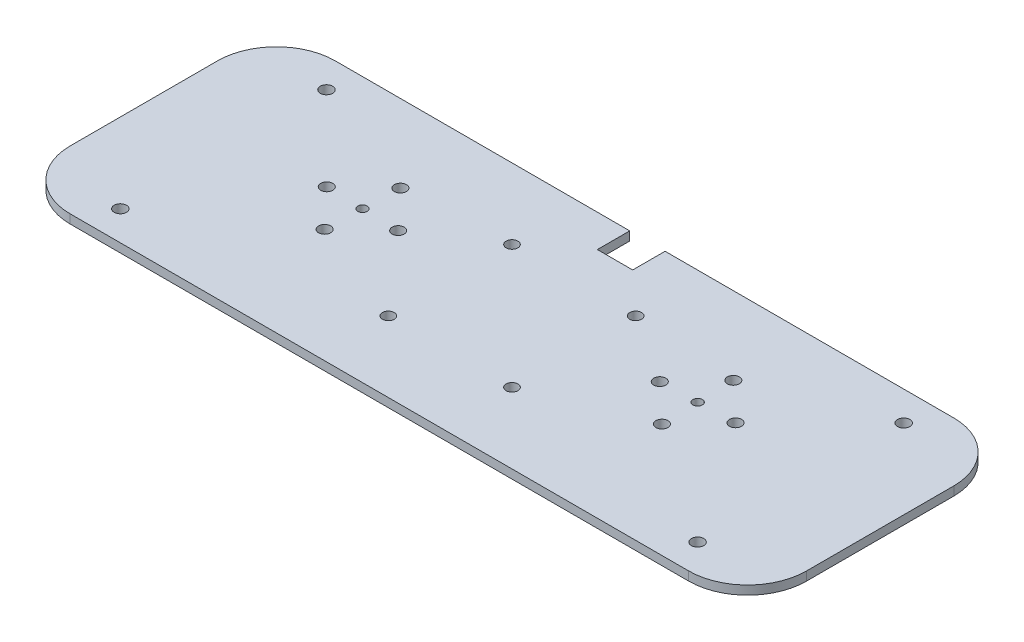
SolidWorks part; units mm, degrees
material "Thornel Mat VMA"
ref_plane "前视基准面" through (0, 0, 0) normal (0, 0, 1) x (1, 0, 0)
ref_plane "上视基准面" through (0, 0, 0) normal (0, 1, 0) x (1, 0, 0)
ref_plane "右视基准面" through (0, 0, 0) normal (1, 0, 0) x (0, 0, -1)
sketch "草图1" plane through (0, 0, 0) normal (0, 0, 1) x (1, 0, 0)
  line L1 (-125, -1.5) -> (125, -1.5)
  line L2 (-125, -1.5) -> (-125, 1.5)
  line L3 (-125, 1.5) -> (125, 1.5)
  line L4 (125, -1.5) -> (125, 1.5)
  line L5 (-125, -1.5) -> (125, 1.5) construction
  line L6 (-125, 1.5) -> (125, -1.5) construction
  point P0 (0, 0)
  dimension "D1" = 3
  dimension "D2" = 250
extrude "凸台-拉伸1" add sketch "草图1" along normal mid plane 90
sketch "草图2" plane through (0, 1.5, 0) normal (0, 1, 0) x (1, 0, 0)
  line L0 (-21, 21) -> (21, 21) construction
  line L1 (21, 21) -> (21, -21) construction
  line L2 (21, -21) -> (-21, -21) construction
  line L3 (-21, -21) -> (-21, 21) construction
  circle A0 centre (-21, 21) radius 2
  circle A1 centre (21, 21) radius 2
  circle A2 centre (21, -21) radius 2
  circle A3 centre (-21, -21) radius 2
  point P8 (21, 0)
  point P9 (0, 21)
  dimension "D1" = 4
  dimension "D2" = 42
  dimension "D3" = 42
extrude "切除-拉伸1" cut sketch "草图2" against normal through all
fillet "圆角1" radius 20 4 edges at (125, 0, 45) (-125, 0, 45) (-125, 0, -45) (125, 0, -45)
sketch "草图4" plane through (0, -1.5, 0) normal (0, -1, 0) x (1, 0, 0)
  line L0 (-98, -35) -> (-98, 35) construction
  line L1 (-98, 35) -> (98, 35) construction
  line L2 (98, 35) -> (98, -35) construction
  line L3 (98, -35) -> (-98, -35) construction
  circle A0 centre (-98, -35) radius 2.1
  circle A1 centre (-98, 35) radius 2.1
  circle A2 centre (98, 35) radius 2.1
  circle A3 centre (98, -35) radius 2.1
  point P8 (0, -35)
  point P9 (-98, 0)
  dimension "D1" = 4.2
  dimension "D2" = 70
  dimension "D3" = 196
extrude "切除-拉伸3" cut sketch "草图4" against normal blind 10
sketch "草图5" plane through (0, -1.5, 0) normal (0, -1, 0) x (1, 0, 0)
  circle A0 centre (57.2731, 6.3593) radius 2.05 construction
  circle A1 centre (69.3984, -6.5045) radius 2.05 construction
  circle A2 centre (44.4093, -5.7659) radius 2.05 construction
  circle A3 centre (56.5346, -18.6297) radius 2.05 construction
  circle A4 centre (57.2731, 6.3593) radius 2.05
  circle A5 centre (69.3984, -6.5045) radius 2.05
  circle A6 centre (44.4093, -5.7659) radius 2.05
  circle A7 centre (56.5346, -18.6297) radius 2.05
extrude "切除-拉伸4" cut sketch "草图5" against normal blind 4
sketch "草图6" plane through (0, 1.5, 0) normal (0, 1, 0) x (1, 0, 0)
  circle A0 centre (56.9038, 6.1352) radius 17 construction
  circle A1 centre (56.9038, 6.1352) radius 17 construction
  circle A2 centre (56.9038, 6.1352) radius 1.6
  dimension "D1" = 3.2
extrude "切除-拉伸5" cut sketch "草图6" against normal blind 4
mirror "镜向1" about plane through (0, 0, 0) normal (1, 0, 0) of "切除-拉伸5", "切除-拉伸4"
sketch "草图7" plane through (0, 1.5, 0) normal (0, 1, 0) x (1, 0, 0)
  line L0 (-5.0201, 58) -> (-5.0201, 34) construction
  line L1 (-5.0201, 45) -> (-5.0201, 34)
  line L2 (105, 45) -> (-105, 45) construction
  line L3 (6.9799, 45) -> (-5.0201, 45)
  line L4 (-5.0201, 34) -> (6.9799, 34)
  line L5 (6.9799, 34) -> (6.9799, 58) construction
  line L6 (6.9799, 34) -> (6.9799, 45)
extrude "切除-拉伸6" cut sketch "草图7" against normal blind 20
